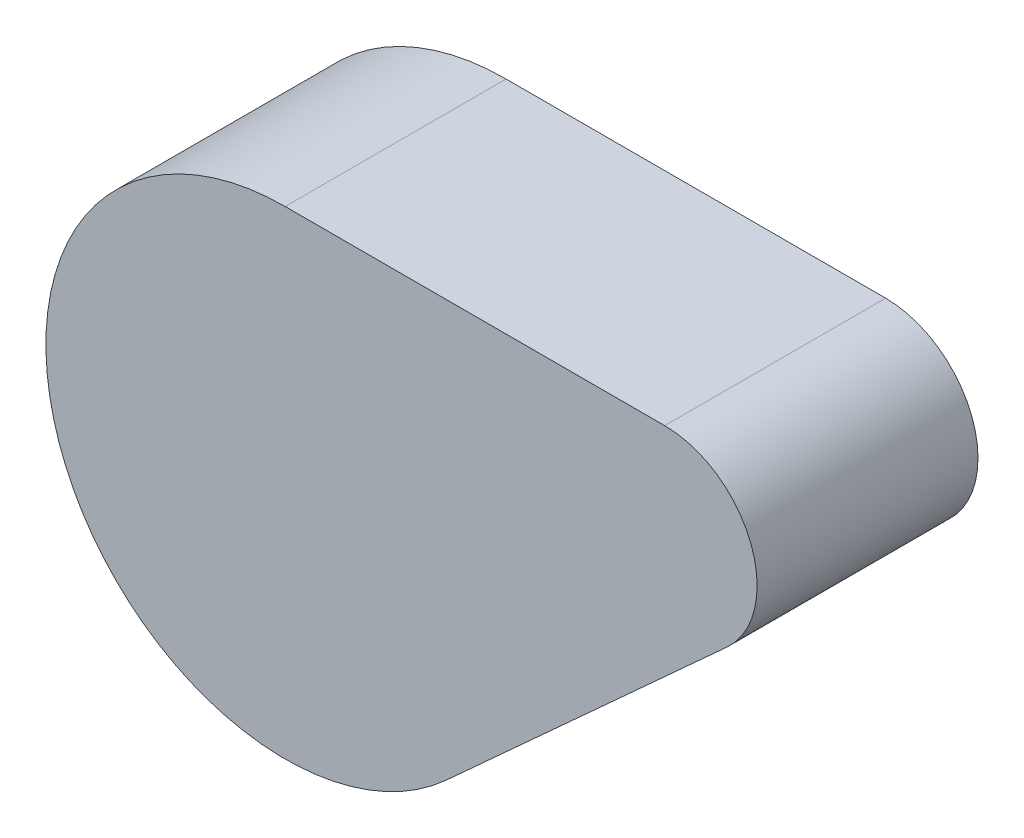
SolidWorks part; units mm, degrees
ref_plane "Alzado" through (0, 0, 0) normal (0, 0, 1) x (1, 0, 0)
ref_plane "Planta" through (0, 0, 0) normal (0, 1, 0) x (1, 0, 0)
ref_plane "Vista lateral" through (0, 0, 0) normal (1, 0, 0) x (0, 0, -1)
sketch "Croquis1" plane through (0, 0, 0) normal (0, 0, 1) x (1, 0, 0)
  line L0 (-6.65, 39.55) -> (44.9, 39.55)
  line L1 (53.3484, 17.7196) -> (15.2284, -16.983)
  line L4 (-981.3218, 39.55) -> (49018.6782, 39.55) construction
  line L5 (-103.5055, 39.55) -> (149.7175, 39.55) construction
  arc A0 (53.3484, 17.7196) -> (44.9, 39.55) centre (44.9, 27) ccw
  arc A1 (-6.65, 39.55) -> (15.2284, -16.983) centre (-6.65, 7.05) ccw
  point P4 (0, 0)
  point P14 (49.8595, 15.4715)
  point P15 (51.7976, 16.5155)
  dimension "D1" = 0
extrude "Saliente-Extruir1" add sketch "Croquis1" along normal blind 30
